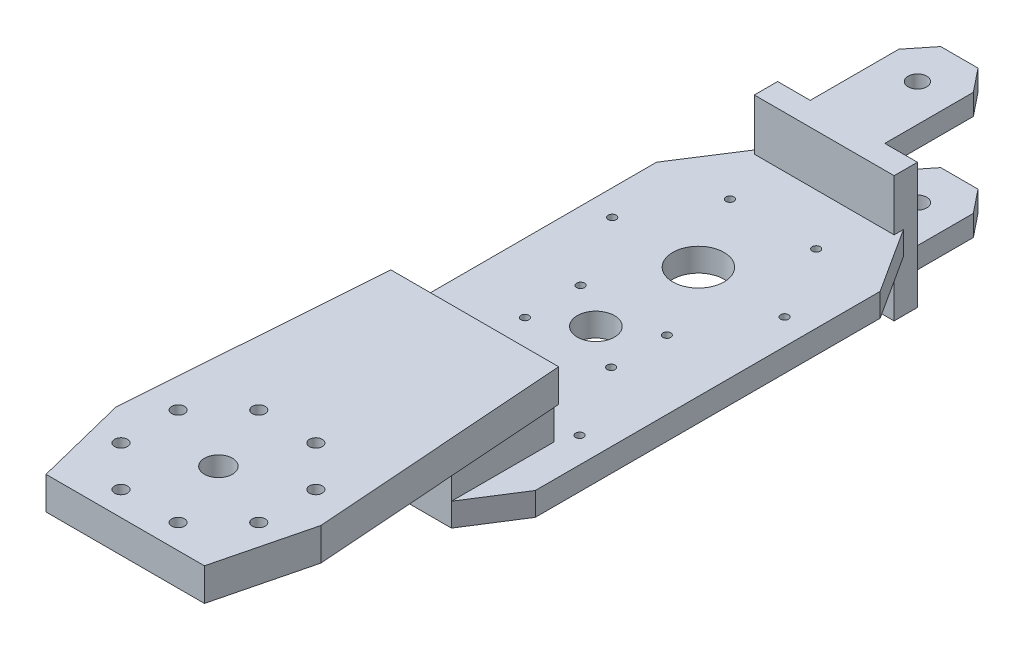
SolidWorks part; units mm, degrees
material "6061-T6 (SS)"
ref_plane "Front Plane" through (0, 0, 0) normal (0, 0, 1) x (1, 0, 0)
ref_plane "Top Plane" through (0, 0, 0) normal (0, 1, 0) x (1, 0, 0)
ref_plane "Right Plane" through (0, 0, 0) normal (1, 0, 0) x (0, 0, -1)
ref_plane "PL_Knee_Plate_base" through (0, 20, 0) normal (0, 1, 0) x (1, 0, 0)
sketch "SK_Knee_Plate" plane through (0, 20, 0) normal (0, 1, 0) x (1, 0, 0)
  line L0 (-34, -40) -> (34, -40)
  line L1 (34, -40) -> (44, 0)
  line L2 (44, 0) -> (36, 110)
  line L3 (36, 110) -> (-36, 110)
  line L4 (-36, 110) -> (-44, 0)
  line L5 (-44, 0) -> (-34, -40)
  circle A0 centre (29.5641, 12.2459) radius 2.75
  circle A1 centre (12.2459, 29.5641) radius 2.75
  circle A2 centre (-12.2459, 29.5641) radius 2.75
  circle A3 centre (-29.5641, 12.2459) radius 2.75
  circle A4 centre (-29.5641, -12.2459) radius 2.75
  circle A5 centre (-12.2459, -29.5641) radius 2.75
  circle A6 centre (12.2459, -29.5641) radius 2.75
  circle A7 centre (29.5641, -12.2459) radius 2.75
  circle A8 centre (0, 0) radius 6
  dimension "D11_SK_Knee_Plate" = 5.5
  dimension "D14_SK_Knee_Plate" = 5.5
  dimension "D17_SK_Knee_Plate" = 5.5
  dimension "D20_SK_Knee_Plate" = 5.5
  dimension "D23_SK_Knee_Plate" = 5.5
  dimension "D26_SK_Knee_Plate" = 5.5
  dimension "D29_SK_Knee_Plate" = 5.5
  dimension "D32_SK_Knee_Plate" = 5.5
  dimension "D35_SK_Knee_Plate" = 12
  dimension "P1" = 34
  dimension "P2" = 40
  dimension "P3" = 34
  dimension "P4" = 40
  dimension "P5" = 44
  dimension "P6" = 36
  dimension "P7" = 110
  dimension "P8" = 36
  dimension "P9" = 110
  dimension "P10" = 44
  dimension "P12" = 29.5641
  dimension "P13" = 12.2459
  dimension "P15" = 12.2459
  dimension "P16" = 29.5641
  dimension "P18" = 12.2459
  dimension "P19" = 29.5641
  dimension "P21" = 29.5641
  dimension "P22" = 12.2459
  dimension "P24" = 29.5641
  dimension "P25" = 12.2459
  dimension "P27" = 12.2459
  dimension "P28" = 29.5641
  dimension "P30" = 12.2459
  dimension "P31" = 29.5641
  dimension "P33" = 29.5641
  dimension "P34" = 12.2459
extrude "Knee_Plate" add sketch "SK_Knee_Plate" along normal blind 14
ref_plane "PL_Knee_Pilot_Recess_base" through (0, 20, 0) normal (0, 1, 0) x (1, 0, 0)
sketch "SK_Knee_Pilot_Recess" plane through (0, 20, 0) normal (0, 1, 0) x (1, 0, 0)
  circle A0 centre (0, 0) radius 25.15
  dimension "D1_SK_Knee_Pilot_Recess" = 50.3
extrude "Knee_Pilot_Recess" cut sketch "SK_Knee_Pilot_Recess" along normal blind 2.2
ref_plane "PL_Joggle_base" through (0, 0, -110) normal (0, 0, 1) x (1, 0, 0)
sketch "SK_Joggle" plane through (0, 0, -110) normal (0, 0, 1) x (1, 0, 0)
  line L0 (-34, 34) -> (34, 34)
  line L1 (34, 34) -> (34, -5)
  line L2 (34, -5) -> (-34, -5)
  line L3 (-34, -5) -> (-34, 34)
  dimension "P1" = 34
  dimension "P2" = 34
  dimension "P3" = 34
  dimension "P4" = 34
  dimension "P5" = 34
  dimension "P6" = 5
  dimension "P7" = 34
  dimension "P8" = 5
extrude "Joggle" add sketch "SK_Joggle" along normal blind 44
ref_plane "PL_Web_base" through (0, -5, 0) normal (0, 1, 0) x (1, 0, 0)
sketch "SK_Web" plane through (0, -5, 0) normal (0, 1, 0) x (1, 0, 0)
  line L0 (-34, 66) -> (34, 66)
  line L1 (34, 66) -> (48, 88)
  line L2 (48, 88) -> (48, 236)
  line L3 (48, 236) -> (30, 264)
  line L4 (30, 264) -> (-30, 264)
  line L5 (-30, 264) -> (-48, 236)
  line L6 (-48, 236) -> (-48, 88)
  line L7 (-48, 88) -> (-34, 66)
  circle A0 centre (37, 118) radius 1.7
  circle A1 centre (18.5, 150.0429) radius 1.7
  circle A2 centre (-18.5, 150.0429) radius 1.7
  circle A3 centre (-37, 118) radius 1.7
  circle A4 centre (-18.5, 85.9571) radius 1.7
  circle A5 centre (18.5, 85.9571) radius 1.7
  circle A6 centre (37, 206) radius 1.7
  circle A7 centre (18.5, 238.0429) radius 1.7
  circle A8 centre (-18.5, 238.0429) radius 1.7
  circle A9 centre (-37, 206) radius 1.7
  circle A10 centre (-18.5, 173.9571) radius 1.7
  circle A11 centre (18.5, 173.9571) radius 1.7
  circle A12 centre (0, 118) radius 11
  circle A13 centre (0, 206) radius 11
  circle A14 centre (0, 162) radius 8
  dimension "D17_SK_Web" = 3.4
  dimension "D20_SK_Web" = 3.4
  dimension "D23_SK_Web" = 3.4
  dimension "D26_SK_Web" = 3.4
  dimension "D29_SK_Web" = 3.4
  dimension "D32_SK_Web" = 3.4
  dimension "D35_SK_Web" = 3.4
  dimension "D38_SK_Web" = 3.4
  dimension "D41_SK_Web" = 3.4
  dimension "D44_SK_Web" = 3.4
  dimension "D47_SK_Web" = 3.4
  dimension "D50_SK_Web" = 3.4
  dimension "D53_SK_Web" = 22
  dimension "D55_SK_Web" = 22
  dimension "D57_SK_Web" = 16
  dimension "P1" = 34
  dimension "P2" = 66
  dimension "P3" = 34
  dimension "P4" = 66
  dimension "P5" = 48
  dimension "P6" = 88
  dimension "P7" = 48
  dimension "P8" = 236
  dimension "P9" = 30
  dimension "P10" = 264
  dimension "P11" = 30
  dimension "P12" = 264
  dimension "P13" = 48
  dimension "P14" = 236
  dimension "P15" = 48
  dimension "P16" = 88
  dimension "P18" = 37
  dimension "P19" = 118
  dimension "P21" = 18.5
  dimension "P22" = 150.0429
  dimension "P24" = 18.5
  dimension "P25" = 150.0429
  dimension "P27" = 37
  dimension "P28" = 118
  dimension "P30" = 18.5
  dimension "P31" = 85.9571
  dimension "P33" = 18.5
  dimension "P34" = 85.9571
  dimension "P36" = 37
  dimension "P37" = 206
  dimension "P39" = 18.5
  dimension "P40" = 238.0429
  dimension "P42" = 18.5
  dimension "P43" = 238.0429
  dimension "P45" = 37
  dimension "P46" = 206
  dimension "P48" = 18.5
  dimension "P49" = 173.9571
  dimension "P51" = 18.5
  dimension "P52" = 173.9571
  dimension "P54" = 118
  dimension "P56" = 206
  dimension "P58" = 162
extrude "Web" add sketch "SK_Web" along normal blind 10
ref_plane "PL_Fork_Bar_base" through (0, 0, -270) normal (0, 0, 1) x (1, 0, 0)
sketch "SK_Fork_Bar" plane through (0, 0, -270) normal (0, 0, 1) x (1, 0, 0)
  line L0 (-30, 27) -> (30, 27)
  line L1 (30, 27) -> (30, -27)
  line L2 (30, -27) -> (-30, -27)
  line L3 (-30, -27) -> (-30, 27)
  dimension "P1" = 30
  dimension "P2" = 27
  dimension "P3" = 30
  dimension "P4" = 27
  dimension "P5" = 30
  dimension "P6" = 27
  dimension "P7" = 30
  dimension "P8" = 27
extrude "Fork_Bar" add sketch "SK_Fork_Bar" along normal blind 10
ref_plane "PL_Tine_Lat_base" through (0, -27, 0) normal (0, 1, 0) x (1, 0, 0)
sketch "SK_Tine_Lat" plane through (0, -27, 0) normal (0, 1, 0) x (1, 0, 0)
  line L0 (-16, 260) -> (16, 260)
  line L1 (16, 260) -> (16, 308)
  line L2 (16, 308) -> (8, 318)
  line L3 (8, 318) -> (-8, 318)
  line L4 (-8, 318) -> (-16, 308)
  line L5 (-16, 308) -> (-16, 260)
  circle A0 centre (0, 300) radius 4
  dimension "D13_SK_Tine_Lat" = 8
  dimension "P1" = 16
  dimension "P2" = 260
  dimension "P3" = 16
  dimension "P4" = 260
  dimension "P5" = 16
  dimension "P6" = 308
  dimension "P7" = 8
  dimension "P8" = 318
  dimension "P9" = 8
  dimension "P10" = 318
  dimension "P11" = 16
  dimension "P12" = 308
  dimension "P14" = 300
extrude "Tine_Lat" add sketch "SK_Tine_Lat" along normal blind 9
ref_plane "PL_Tine_Med_base" through (0, 18, 0) normal (0, 1, 0) x (1, 0, 0)
sketch "SK_Tine_Med" plane through (0, 18, 0) normal (0, 1, 0) x (1, 0, 0)
  line L0 (-16, 260) -> (16, 260)
  line L1 (16, 260) -> (16, 308)
  line L2 (16, 308) -> (8, 318)
  line L3 (8, 318) -> (-8, 318)
  line L4 (-8, 318) -> (-16, 308)
  line L5 (-16, 308) -> (-16, 260)
  circle A0 centre (0, 300) radius 4
  dimension "D13_SK_Tine_Med" = 8
  dimension "P1" = 16
  dimension "P2" = 260
  dimension "P3" = 16
  dimension "P4" = 260
  dimension "P5" = 16
  dimension "P6" = 308
  dimension "P7" = 8
  dimension "P8" = 318
  dimension "P9" = 8
  dimension "P10" = 318
  dimension "P11" = 16
  dimension "P12" = 308
  dimension "P14" = 300
extrude "Tine_Med" add sketch "SK_Tine_Med" along normal blind 9
ref_plane "PL_AnkleZ" through (0, 0, -300) normal (0, 0, 1) x (1, 0, 0)
ref_axis "AX_AnklePitch" through (0, 37.05, -300) along (0, -1, 0)
ref_axis "AX_KneeY" through (0, 37.05, 0) along (0, -1, 0)
ref_plane "PL_KneeRef" through (0, 0, 0) normal (-0.9239, 0, 0.3827) x (0, -1, 0)
equation "\"Shin_length\"= 300"
equation "\"AnkleA_z\"= -118"
equation "\"AnkleB_z\"= -206"
